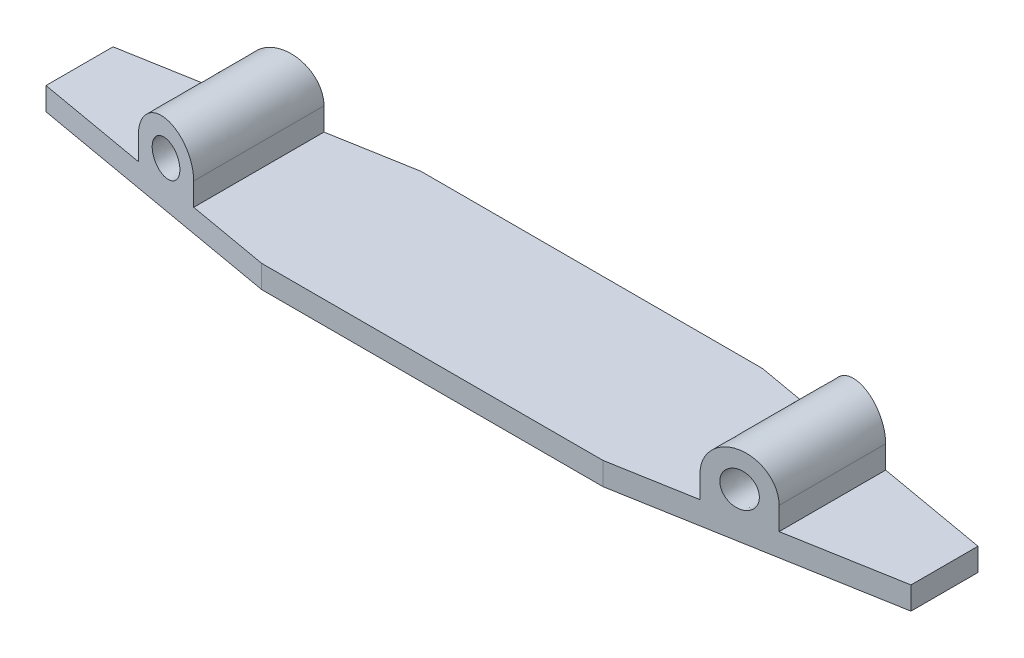
SolidWorks part; units mm, degrees
ref_plane "Front Plane" through (0, 0, 0) normal (0, 0, 1) x (1, 0, 0)
ref_plane "Top Plane" through (0, 0, 0) normal (0, 1, 0) x (1, 0, 0)
ref_plane "Right Plane" through (0, 0, 0) normal (1, 0, 0) x (0, 0, -1)
sketch "Body" plane through (0, 0, 0) normal (0, 1, 0) x (1, 0, 0)
  line L0 (0, 70) -> (-115, 49.7224)
  line L1 (0, 0) -> (150, 0)
  line L2 (0, 0) -> (0, 70)
  line L3 (0, 70) -> (150, 70)
  line L4 (150, 0) -> (150, 70)
  line L5 (-115, 49.7224) -> (-115, 20.2776)
  line L6 (-115, 20.2776) -> (0, 0)
  line L7 (150, 70) -> (265, 49.7224)
  line L8 (265, 49.7224) -> (265, 20.2776)
  line L9 (265, 20.2776) -> (150, 0)
  dimension "D1" = 150
  dimension "D2" = 380
  dimension "D3" = 80
  dimension "D4" = 115
  dimension "D5" = 80
  dimension "D6" = 70
extrude "Body Boss-Extrude" add sketch "Body" along normal blind 10 from surface contours L5 L6 L2 L0 | L9 L8 L7 L4 | L1 L4 L3 L2 region at (-49.6835, 0, -35) region at (75, 0, -35) region at (199.6835, 0, -35) starting at plane "Top Plane"
ref_plane "Plane2" through (0, 0, 0) normal (-0.1736, 0, 0.9848) x (0.9848, 0, 0.1736)
sketch "Drive Shaft Mount" plane through (0, 0, 0) normal (-0.1736, 0, 0.9848) x (0.9848, 0, 0.1736)
  line L0 (-66.7741, 10) -> (-66.7741, 20)
  line L1 (0, 10) -> (-116.7741, 10) construction
  line L3 (-36.7741, 20) -> (-36.7741, 10)
  line L4 (-36.7741, 10) -> (-66.7741, 10)
  line L5 (-116.7741, 10) -> (-116.7741, 0) construction
  arc A0 (-66.7741, 20) -> (-36.7741, 20) centre (-51.7741, 20) cw
  circle A1 centre (-51.7741, 20) radius 7.5
  dimension "D2" = 30
  dimension "D4" = 7.5
  dimension "D1" = 10
  dimension "D3" = 50
ref_plane "Plane3" through (-11.9707, 0, -67.8892) normal (-0.1736, 0, -0.9848) x (-0.9848, 0, 0.1736)
extrude "Mount Boss-Extrude4" add sketch "Drive Shaft Mount" along direction (0, 0, -1) on the side against the normal up to surface (57.2285 mm away) from surface up to plane "Plane3" starting at plane "Plane2"
ref_axis "Axis1" through (75, 10, -70) along (0, 0, 1)
ref_plane "Plane4" through (75, 0, 0) normal (1, 0, 0) x (0, 0, -1)
ref_plane "Plane5" through (4.5231, 0, 25.6515) normal (0.1736, 0, 0.9848) x (0.9848, 0, -0.1736)
ref_plane "Plane6" through (16.4938, 0, -93.5408) normal (-0.1736, 0, 0.9848) x (0.9848, 0, 0.1736)
sketch "Sketch7" plane through (4.5231, 0, 25.6515) normal (0.1736, 0, 0.9848) x (0.9848, 0, -0.1736)
  line L0 (184.4952, 10) -> (184.4952, 20)
  line L1 (214.4952, 20) -> (214.4952, 10)
  line L2 (214.4952, 10) -> (184.4952, 10)
  line L3 (147.7212, 10) -> (264.4952, 10) construction
  line L4 (264.4952, 10) -> (264.4952, 0) construction
  arc A0 (184.4952, 20) -> (214.4952, 20) centre (199.4952, 20) cw
  circle A1 centre (199.4952, 20) radius 7.5
  point P6 (228.7155, 10)
  dimension "D3" = 7.5
  dimension "D1" = 10
  dimension "D2" = 30
  dimension "D4" = 50
extrude "Boss-Extrude5" add sketch "Sketch7" along direction (0, 0, -1) on the side against the normal up to surface (46.8096 mm away) from surface up to plane "Plane6" starting at plane "Plane5"
